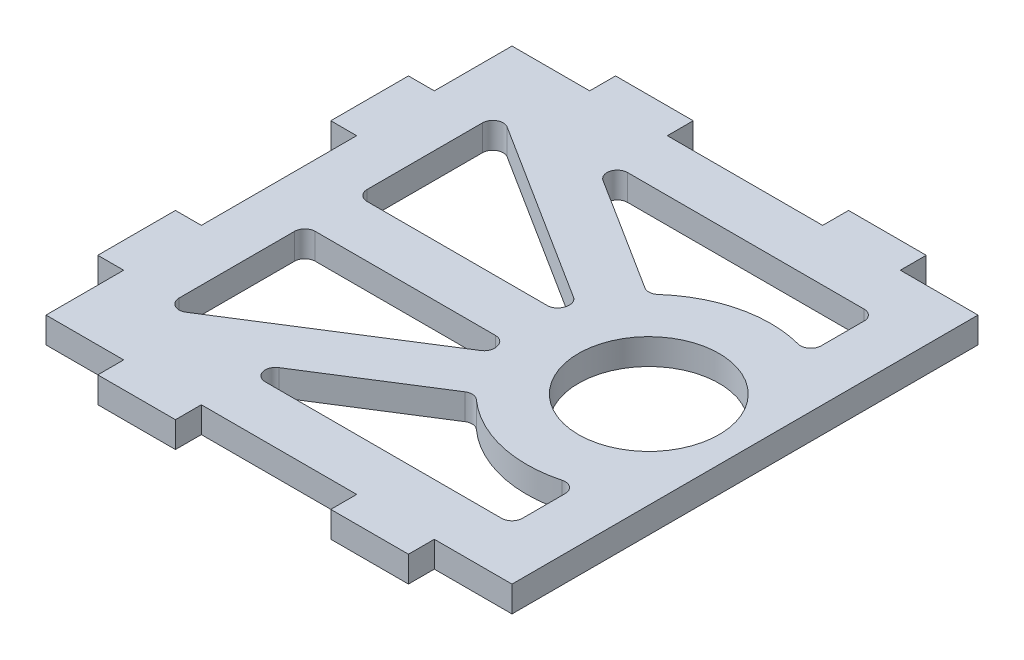
SolidWorks part; units mm, degrees
ref_plane "Front Plane" through (0, 0, 0) normal (0, 0, 1) x (1, 0, 0)
ref_plane "Top Plane" through (0, 0, 0) normal (0, 1, 0) x (1, 0, 0)
ref_plane "Right Plane" through (0, 0, 0) normal (1, 0, 0) x (0, 0, -1)
sketch "Sketch1" plane through (0, 0, 0) normal (0, 1, 0) x (1, 0, 0)
  line L0 (0, 57.15) -> (184.6638, 57.15) construction
  line L1 (0, 0) -> (19.05, 0)
  line L2 (0, 0) -> (0, 19.05)
  line L3 (0, 114.3) -> (19.05, 114.3)
  line L4 (114.3, 0) -> (114.3, 114.3)
  line L5 (38.1, 0) -> (76.2, 0)
  line L7 (95.25, 0) -> (95.25, -6.35)
  line L8 (95.25, -6.35) -> (76.2, -6.35)
  line L9 (76.2, 0) -> (76.2, -6.35)
  line L11 (19.05, 0) -> (19.05, -6.35)
  line L12 (19.05, -6.35) -> (38.1, -6.35)
  line L13 (38.1, 0) -> (38.1, -6.35)
  line L14 (95.25, 0) -> (114.3, 0)
  line L15 (38.1, 114.3) -> (38.1, 120.65)
  line L16 (19.05, 120.65) -> (38.1, 120.65)
  line L17 (19.05, 114.3) -> (19.05, 120.65)
  line L18 (76.2, 114.3) -> (76.2, 120.65)
  line L19 (95.25, 120.65) -> (76.2, 120.65)
  line L20 (95.25, 114.3) -> (95.25, 120.65)
  line L21 (38.1, 114.3) -> (76.2, 114.3)
  line L23 (95.25, 114.3) -> (114.3, 114.3)
  line L24 (-6.35, 19.05) -> (-6.35, 38.1)
  line L25 (0, 95.25) -> (-6.35, 95.25)
  line L27 (0, 76.2) -> (-6.35, 76.2)
  line L28 (-6.35, 95.25) -> (-6.35, 76.2)
  line L29 (0, 38.1) -> (-6.35, 38.1)
  line L31 (0, 19.05) -> (-6.35, 19.05)
  line L32 (0, 95.25) -> (0, 114.3)
  line L33 (0, 38.1) -> (0, 76.2)
  dimension "D1" = 114.3
  dimension "D2" = 114.3
  dimension "D3" = 19.05
  dimension "D4" = 19.05
  dimension "D5" = 19.05
  dimension "D6" = 19.05
  dimension "D7" = 6.35
  dimension "D8" = 6.35
  dimension "D9" = 19.05
  dimension "D10" = 19.05
extrude "Boss-Extrude1" add sketch "Sketch1" against normal blind 6.35
sketch "Sketch2" plane through (0, 0, 0) normal (0, 1, 0) x (1, 0, 0)
  line L0 (114.3, 57.15) -> (55.59, 57.15) construction
  line L1 (114.3, 0) -> (114.3, 114.3) construction
  line L2 (107.95, 57.15) -> (107.95, 78.6846) construction
  circle A0 centre (90.7, 57.15) radius 17.25
  dimension "D1" = 34.5001
  dimension "D2" = 6.35
extrude "Cut-Extrude1" cut sketch "Sketch2" against normal through all
sketch "Sketch3" plane through (0, 0, 0) normal (0, 1, 0) x (1, 0, 0)
  line L0 (90.7, 57.15) -> (-12.2602, 122.2732) construction
  line L1 (87.3056, 51.7834) -> (-15.6546, 116.9066)
  line L2 (94.0944, 62.5166) -> (-8.8658, 127.6398)
  line L3 (90.7, 57.15) -> (22.3264, 57.15) construction
  line L4 (90.7, 57.15) -> (-12.2602, -7.9732) construction
  line L5 (87.3056, 62.5166) -> (-15.6546, -2.6066)
  line L6 (94.0944, 51.7834) -> (-8.8658, -13.3398)
  line L35 (90.7, 57.15) -> (-12.2602, 57.15) construction
  line L36 (90.7, 50.8) -> (-12.2602, 50.8)
  line L37 (90.7, 63.5) -> (-12.2602, 63.5)
  line L63 (12.7, 12.7) -> (101.6, 12.7)
  line L64 (101.6, 12.7) -> (101.6, 101.6)
  line L65 (101.6, 101.6) -> (12.7, 101.6)
  line L66 (12.7, 101.6) -> (12.7, 12.7)
  line L67 (12.7, 12.7) -> (101.6, 12.7)
  line L68 (101.6, 12.7) -> (101.6, 101.6)
  line L69 (101.6, 101.6) -> (12.7, 101.6)
  line L70 (12.7, 101.6) -> (12.7, 12.7)
  arc A0 (87.3056, 51.7834) -> (94.0944, 62.5166) centre (90.7, 57.15) ccw
  arc A1 (-8.8658, 127.6398) -> (-15.6546, 116.9066) centre (-12.2602, 122.2732) ccw
  arc A3 (87.3056, 62.5166) -> (94.0944, 51.7834) centre (90.7, 57.15) cw
  circle A4 centre (90.7, 57.15) radius 29.95
  circle A5 centre (90.7, 57.15) radius 29.95
  arc A6 (-8.8658, -13.3398) -> (-15.6546, -2.6066) centre (-12.2602, -7.9732) cw
  arc A7 (90.7, 50.8) -> (90.7, 63.5) centre (90.7, 57.15) ccw
  arc A8 (-12.2602, 63.5) -> (-12.2602, 50.8) centre (-12.2602, 57.15) ccw
  point P2 (39.2199, 89.7116)
  point P8 (39.2199, 24.5884)
  point P19 (39.2199, 57.15)
  dimension "D2" = 6.35
  dimension "D1" = 12.7
  dimension "D3" = 12.7
extrude "Cut-Extrude2" cut sketch "Sketch3" against normal through all contours A5 L68 L69 L2 | A5 L1 L70 L37 | A5 L36 L70 L5 | A5 L6 L67 L68 region at (30.9036, 0, -75.4809) region at (30.9036, 0, -38.8191) region at (72.1425, 0, -20.8641) region at (72.1425, 0, -93.4359)
fillet "Fillet1" radius 2.54 16 edges at (61.4308, -3.175, -63.5) (12.7, -3.175, -63.5) (62.5692, -3.175, -67.4293) (101.6, -3.175, -29.2539) (101.6, -3.175, -12.7) (32.3033, -3.175, -12.7) (69.3581, -3.175, -36.1375) (69.3581, -3.175, -78.1625) (32.3033, -3.175, -101.6) (101.6, -3.175, -101.6) (101.6, -3.175, -85.0461) (62.5692, -3.175, -46.8707) (12.7, -3.175, -15.328) (12.7, -3.175, -50.8) (61.4308, -3.175, -50.8) (12.7, -3.175, -98.972)
